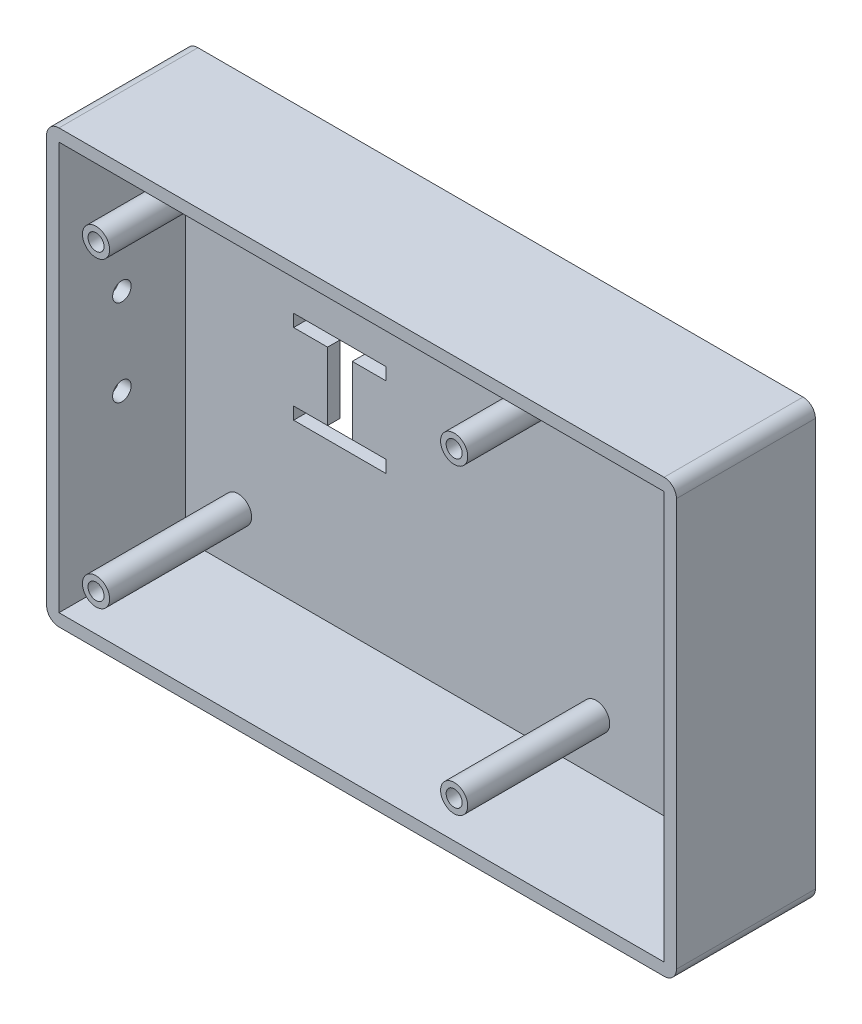
SolidWorks part; units mm, degrees
ref_plane "Front Plane" through (0, 0, 0) normal (0, 0, 1) x (1, 0, 0)
ref_plane "Top Plane" through (0, 0, 0) normal (0, 1, 0) x (1, 0, 0)
ref_plane "Right Plane" through (0, 0, 0) normal (1, 0, 0) x (0, 0, -1)
sketch "Sketch1" plane through (0, 0, 0) normal (0, 0, 1) x (1, 0, 0)
  line L0 (-5, -5) -> (93, -5)
  line L5 (3.5, 56) -> (3.5, 52.5)
  line L6 (-5, -5) -> (-5, 61)
  line L7 (-5, 61) -> (93, 61)
  line L8 (93, 0) -> (93, 56)
  line L9 (93, -5) -> (93, 0)
  line L10 (93, 56) -> (93, 61)
  line L13 (-5, 63) -> (93, 63)
  line L14 (95, 56) -> (95, 61)
  line L15 (95, 0) -> (95, 56)
  line L16 (95, -5) -> (95, 0)
  line L17 (-5, -7) -> (93, -7)
  line L18 (-7, -5) -> (-7, 61)
  line L19 (-7, -7) -> (95, -7) construction
  line L20 (-7, -7) -> (-7, 63) construction
  line L21 (95, -7) -> (95, 0) construction
  line L22 (-7, 63) -> (95, 63) construction
  line L23 (95, 56) -> (95, 63) construction
  circle A0 centre (3.5, 52.5) radius 1.3
  circle A1 centre (61.5, 52.5) radius 1.3
  circle A2 centre (61.5, 3.5) radius 1.3
  circle A3 centre (3.5, 3.5) radius 1.3
  circle A4 centre (3.5, 52.5) radius 2.2
  circle A5 centre (61.5, 52.5) radius 2.2
  circle A6 centre (61.5, 3.5) radius 2.2
  circle A7 centre (3.5, 3.5) radius 2.2
  arc A8 (-5, -7) -> (-7, -5) centre (-5, -5) cw
  arc A9 (95, -5) -> (93, -7) centre (93, -5) cw
  arc A10 (93, 63) -> (95, 61) centre (93, 61) cw
  arc A11 (-5, 63) -> (-7, 61) centre (-5, 61) ccw
  dimension "D1" = 2
  dimension "D5" = 2
  dimension "D6" = 2
  dimension "D2" = 2
extrude "Boss-Extrude1" add sketch "Sketch1" along normal blind 2 contours L6 L7 L10 L8 L9 L0
extrude "Boss-Extrude2" add sketch "Sketch1<5>" along normal blind 22.5 contours L13 A11 L18 A8 L17 A9 L16 L15 L14 A10 L10 L8 L9 L0 L6 L7 region at (44, 61.7629, 0)
sketch "Sketch1<5>" plane through (0, 0, 0) normal (0, 0, 1) x (1, 0, 0) same geometry as "Sketch1"
extrude "Boss-Extrude3" add sketch "Sketch1<6>" along normal blind 25 contours A7 A3 | A6 A2 | A5 A1 | A4 A0 region at (5.0116, 54.0116, 0) region at (59.3622, 52.5, 0) region at (59.3622, 3.5, 0) region at (1.3622, 3.5, 0)
sketch "Sketch1<6>" plane through (0, 0, 0) normal (0, 0, 1) x (1, 0, 0) same geometry as "Sketch1"
sketch "Sketch2" plane through (0, 0, 0) normal (0, 0, -1) x (-1, 0, 0)
  line L0 (5, 28) -> (-12.5, 28)
  line L1 (5, -5) -> (5, 61) construction
  line L5 (-20, 20.5) -> (-12.5, 20.5)
  line L6 (-12.5, 22.5) -> (-12.5, 20.5)
  line L7 (-27.5, 22.5) -> (-27.5, 20.5)
  line L8 (-20, 20.5) -> (-27.5, 20.5)
  line L10 (-20, 35.5) -> (-27.5, 35.5)
  line L11 (-27.5, 33.5) -> (-27.5, 35.5)
  line L13 (-12.5, 33.5) -> (-12.5, 35.5)
  line L14 (-20, 35.5) -> (-12.5, 35.5)
  line L15 (-18, 28) -> (-18, 22.5)
  line L16 (-18, 22.5) -> (-12.5, 22.5)
  line L17 (-18, 28) -> (-18, 33.5)
  line L18 (-18, 33.5) -> (-12.5, 33.5)
  line L19 (-22, 22.5) -> (-27.5, 22.5)
  line L20 (-22, 28) -> (-22, 22.5)
  line L21 (-22, 28) -> (-22, 33.5)
  line L22 (-22, 33.5) -> (-27.5, 33.5)
  line L23 (-20, 28) -> (-20, 20.5) construction
  point P19 (-20, 28)
  dimension "D1" = 4
  dimension "D2" = 2
extrude "Cut-Extrude1" cut sketch "Sketch2" against normal blind 25 contours L22 L21 L20 L19 L7 L8 L5 L6 L16 L15 L17 L18 L13 L14 L10 L11 region at (20, 28, 0)
sketch "Sketch3" plane through (-7, 0, 0) normal (-1, 0, 0) x (0, 0, 1)
  line L0 (22.5, 28) -> (12.3117, 28)
  line L1 (22.5, -5) -> (22.5, 61) construction
  line L2 (12.3117, 28) -> (12.3117, 35)
  circle A0 centre (12.3117, 35) radius 1.5
  circle A1 centre (12.3117, 21) radius 1.5
extrude "Cut-Extrude2" cut sketch "Sketch3" against normal blind 25 contours A1 | A0 region at (-7, 33.9693, 13.3424) region at (-7, 21, 12.3117)
